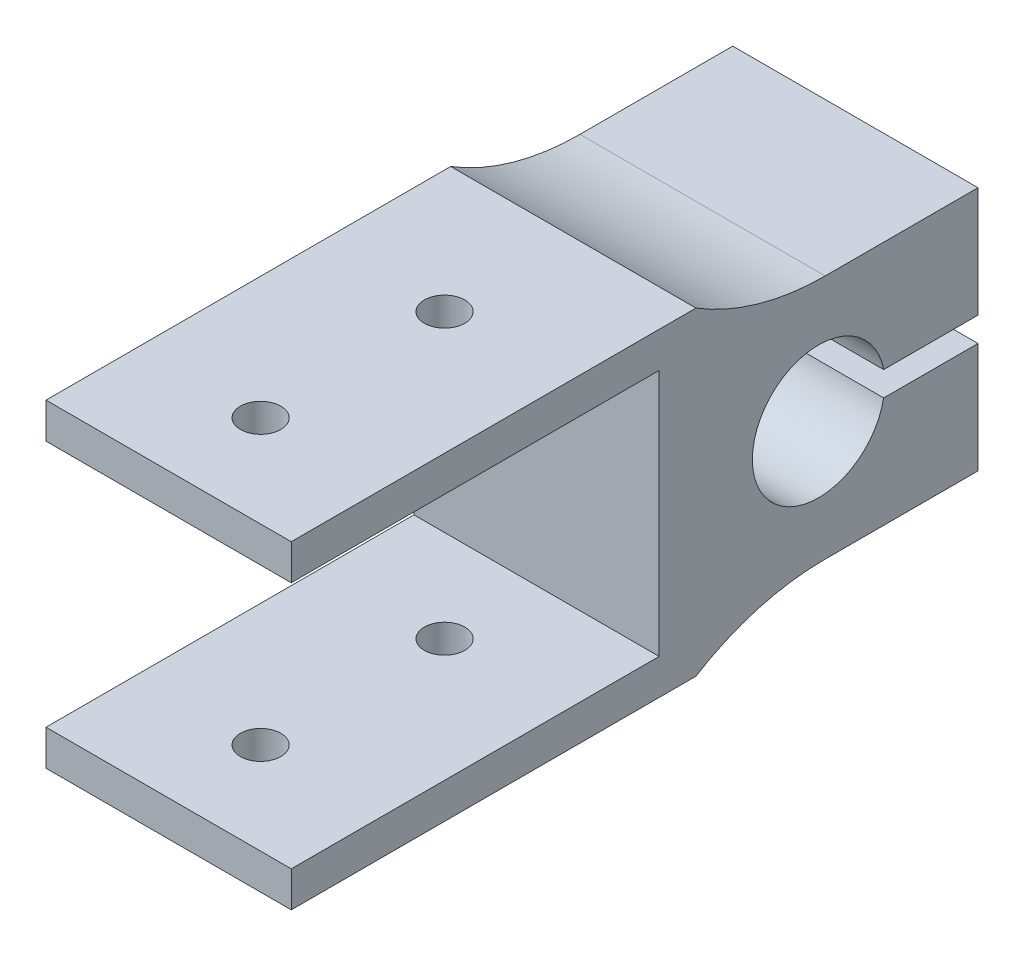
SolidWorks part; units mm, degrees
material "PETG"
ref_plane "Спереди" through (0, 0, 0) normal (0, 0, 1) x (1, 0, 0)
ref_plane "Сверху" through (0, 0, 0) normal (0, 1, 0) x (1, 0, 0)
ref_plane "Справа" through (0, 0, 0) normal (1, 0, 0) x (0, 0, -1)
sketch "Эскиз2" plane through (0, 0, 0) normal (0, 0, 1) x (1, 0, 0)
  line L1 (10, 13) -> (-10, 13)
  line L2 (10, 13) -> (10, -13)
  line L3 (10, -13) -> (-10, -13)
  line L4 (-10, 13) -> (-10, -13)
  line L5 (10, 13) -> (-10, -13) construction
  line L6 (10, -13) -> (-10, 13) construction
  point P0 (0, 0)
  dimension "D1" = 20
  dimension "D2" = 26
extrude "Бобышка-Вытянуть1" add sketch "Эскиз2" along normal blind 3
sketch "Эскиз3" plane through (0, 0, 3) normal (0, 0, 1) x (1, 0, 0)
  line L0 (0, 0) -> (-50000, 0) construction
  line L1 (10, -13) -> (10, 13) construction
  line L2 (-10, 13) -> (10, 13)
  line L3 (-10, 13) -> (-10, 10.1)
  line L4 (-10, 10.1) -> (10, 10.1)
  line L5 (10, 13) -> (10, 10.1)
  line L6 (-10, -10.1) -> (10, -10.1)
  line L7 (10, -13) -> (10, -10.1)
  line L8 (-10, -13) -> (10, -13)
  line L9 (-10, -13) -> (-10, -10.1)
  dimension "D1" = 20.2
extrude "Бобышка-Вытянуть2" add sketch "Эскиз3" along normal blind 30
sketch "Эскиз4" plane through (0, 13, 0) normal (0, 1, 0) x (1, 0, 0)
  line L0 (-2.6915, -3) -> (-50002.6915, -3) construction
  line L2 (10, -3) -> (-10, -3) construction
  line L3 (0, 0) -> (0, -50000) construction
  line L4 (10, 0) -> (-10, 0) construction
  line L5 (10, -33) -> (-10, -33) construction
  circle A0 centre (0, -10.5) radius 1.65
  circle A1 centre (0, -25.5) radius 1.65
  point P8 (0, 0)
  dimension "D1" = 3.3
  dimension "D4" = 7.5
  dimension "D2" = 15
  dimension "D3" = 7.5
extrude "Вырез-Вытянуть1" cut sketch "Эскиз4" against normal up to surface (2.9 mm away) up to face at (0, 10.1, 18)
mirror "Зеркальное отражение1" about plane through (0, 0, 0) normal (0, 1, 0) of "Вырез-Вытянуть1"
sketch "Эскиз5" plane through (0, 0, 0) normal (0, 0, -1) x (-1, 0, 0)
  line L0 (-10, -13) -> (-10, 13) construction
  line L1 (10, 10) -> (-10, 10)
  line L2 (10, 10) -> (10, -10)
  line L3 (10, -10) -> (-10, -10)
  line L4 (-10, 10) -> (-10, -10)
  line L5 (10, 10) -> (-10, -10) construction
  line L6 (10, -10) -> (-10, 10) construction
  point P0 (0, 0)
extrude "Бобышка-Вытянуть3" add sketch "Эскиз5" along normal blind 20
sketch "Эскиз6" plane through (10, 0, 0) normal (1, 0, 0) x (0, 0, -1)
  line L0 (20, 10) -> (0, -10) construction
  line L1 (0, 10) -> (20, -10) construction
  line L3 (20, 10) -> (20, -10) construction
  circle A0 centre (10, 0) radius 5.4
  dimension "D1" = 10.8
  dimension "D2" = 4.6
extrude "Вырез-Вытянуть2" cut sketch "Эскиз6" against normal up to surface (20 mm away) up to face at (-10, 0, 8.1667)
sketch "Эскиз7" plane through (10, 0, 0) normal (1, 0, 0) x (0, 0, -1)
  line L0 (0, 0) -> (50000, 0) construction
  line L1 (15.3066, 1) -> (20, 1)
  line L2 (20, 10) -> (20, -10) construction
  line L3 (20, 1) -> (20, -1)
  line L4 (20, -1) -> (15.3066, -1)
  circle A0 centre (10, 0) radius 5.4 construction
  arc A1 (15.3066, -1) -> (15.3066, 1) centre (10, 0) ccw
  dimension "D1" = 2
extrude "Вырез-Вытянуть3" cut sketch "Эскиз7" against normal up to surface (20 mm away) up to face at (-10, 5.4, -10)
sketch "Эскиз8" plane through (0, 0, -20) normal (0, 0, -1) x (-1, 0, 0)
  line L4 (-10, 10) -> (-10, 1)
  line L5 (-10, 1) -> (10, 1)
  line L6 (10, 1) -> (10, 10)
  line L7 (10, 10) -> (-10, 10)
  line L8 (-10, 10) -> (-10, 1)
  line L9 (-10, 1) -> (10, 1)
  line L10 (10, 1) -> (10, 10)
  line L11 (10, 10) -> (-10, 10)
  line L12 (10, -10) -> (10, -1)
  line L13 (10, -1) -> (-10, -1)
  line L14 (-10, -1) -> (-10, -10)
  line L15 (-10, -10) -> (10, -10)
  line L16 (10, -10) -> (10, -1)
  line L17 (10, -1) -> (-10, -1)
  line L18 (-10, -1) -> (-10, -10)
  line L19 (-10, -10) -> (10, -10)
  dimension "D1" = 0
  dimension "D2" = 0
extrude "Бобышка-Вытянуть4" add sketch "Эскиз8" along normal blind 3
sketch "Эскиз9" plane through (0, -10, 0) normal (0, -1, 0) x (1, 0, 0)
  line L0 (10, -23) -> (-10, -15.3066) construction
  line L1 (10, -15.3066) -> (-10, -23) construction
  line L4 (-10, -15.3066) -> (-10, -23)
  line L5 (-10, -23) -> (10, -23)
  line L6 (10, -23) -> (10, -15.3066)
  line L7 (10, -15.3066) -> (-10, -15.3066)
  line L8 (-10, -15.3066) -> (-10, -23) construction
  line L9 (-10, -23) -> (10, -23) construction
  line L10 (10, -23) -> (10, -15.3066) construction
  line L11 (10, -15.3066) -> (-10, -15.3066) construction
  circle A0 centre (0, -19.1533) radius 1.65
  dimension "D2" = 3.3
  dimension "D1" = 0
extrude "Вырез-Вытянуть4" cut sketch "Эскиз9" against normal offset from surface (16 mm away) 5 up to face at (0, 1, -19.1533) offset beyond the face yes
sketch "Эскиз10" plane through (0, -10, 0) normal (0, -1, 0) x (1, 0, 0)
  circle A0 centre (0, -19.1533) radius 3
  dimension "D1" = 6
extrude "Вырез-Вытянуть5" cut sketch "Эскиз10" against normal blind 3.5
sketch "Эскиз11" plane through (0, 1, 0) normal (0, -1, 0) x (1, 0, 0)
  line L0 (10, -23) -> (-10, -23) construction
  line L2 (3, -23) -> (3, -17.4212)
  line L3 (3, -17.4212) -> (0, -15.6892)
  line L4 (0, -15.6892) -> (-3, -17.4212)
  line L5 (-3, -17.4212) -> (-3, -23)
  line L7 (-4.6321, -19.943) -> (-1.6321, -21.6751) [skipped]
  line L8 (-1.6321, -23.5597) -> (1.3679, -21.8277) [skipped]
  line L9 (-3, -23) -> (3, -23)
  circle A0 centre (0, -19.1533) radius 3 construction
  dimension "D1" = 6
extrude "Вырез-Вытянуть6" cut sketch "Эскиз11" against normal blind 3 from offset 2 offset against normal yes
sketch "Эскиз12" plane through (0, 6, 0) normal (0, -1, 0) x (1, 0, 0)
  circle A0 centre (0, -19.1533) radius 1.65 construction
  circle A1 centre (0, -19.1533) radius 1.65
extrude "Вырез-Вытянуть7" cut sketch "Эскиз12" against normal blind 2
fillet "Скругление1" radius 20 2 edges at (0, -10, 0) (0, 10, 0)
